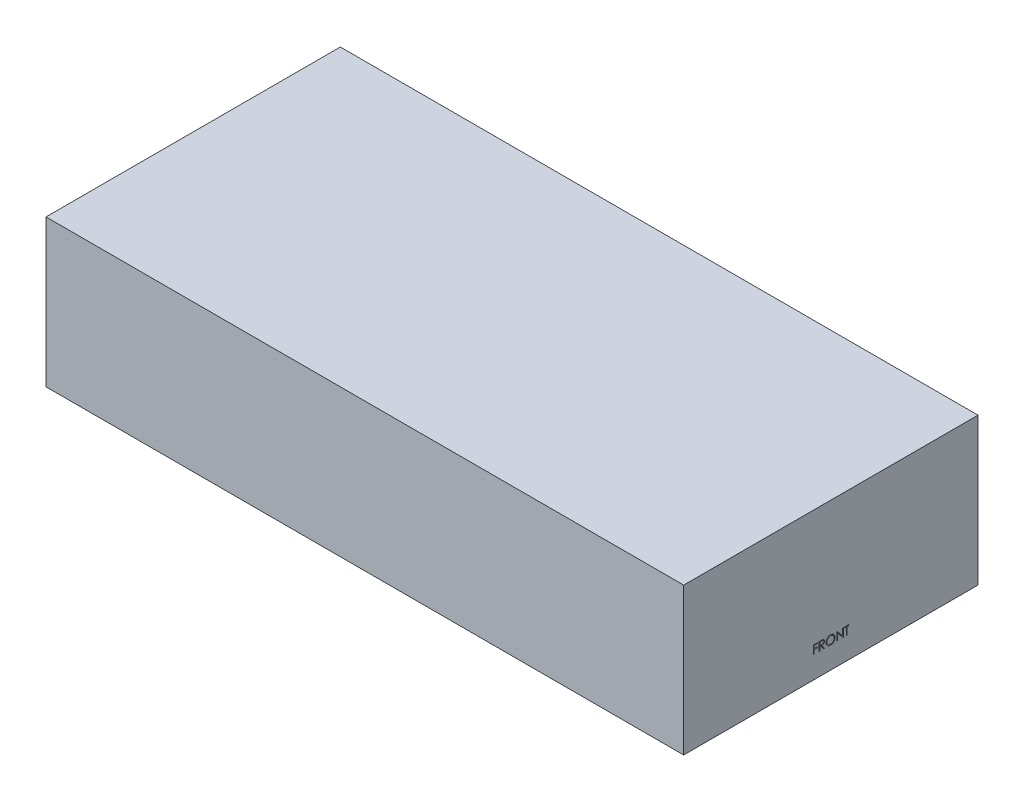
SolidWorks part; units mm, degrees
material "ABS"
ref_plane "Front Plane" through (0, 0, 0) normal (0, 0, 1) x (1, 0, 0)
ref_plane "Top Plane" through (0, 0, 0) normal (0, 1, 0) x (1, 0, 0)
ref_plane "Right Plane" through (0, 0, 0) normal (1, 0, 0) x (0, 0, -1)
ref_axis "X" through (-88.99, 0, 0) along (1, 0, 0)
ref_axis "Y" through (0, 55, 0) along (0, -1, 0)
ref_axis "Z" through (0, 0, -88.99) along (0, 0, 1)
sketch "Sketch1" plane through (0, 0, 0) normal (0, 1, 0) x (1, 0, 0)
  line L1 (-130, 60) -> (130, 60)
  line L2 (-130, 60) -> (-130, -60)
  line L3 (-130, -60) -> (130, -60)
  line L4 (130, 60) -> (130, -60)
  line L5 (-130, 60) -> (130, -60) construction
  line L6 (-130, -60) -> (130, 60) construction
  point P0 (0, 0)
  dimension "D1" = 120
  dimension "D2" = 260
extrude "Boss-Extrude1" add sketch "Sketch1" along normal blind 60
shell "Shell1" [suppressed] thickness 5
sketch "Sketch2" plane through (130, 0, 0) normal (1, 0, 0) x (0, 0, -1)
  line L0 (-9.9936, 8.916) -> (9.9936, 8.916) construction
  line L1 (0, 0) -> (0, 8.916) construction
  text T0 "FRONT"
extrude "Cut-Extrude1" cut sketch "Sketch2" against normal blind 1
